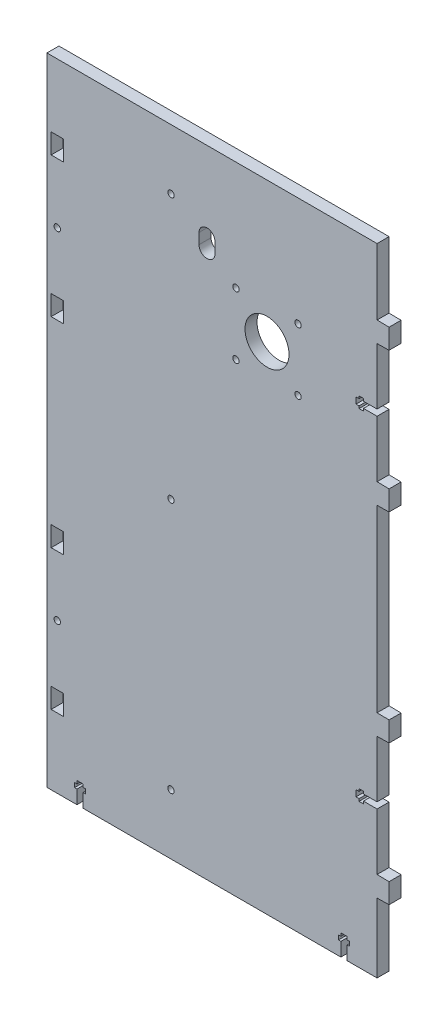
SolidWorks part; units mm, degrees
material "Клен"
ref_plane "Front" through (0, 0, 0) normal (0, 0, 1) x (1, 0, 0)
ref_plane "Top" through (0, 0, 0) normal (0, 1, 0) x (1, 0, 0)
ref_plane "Right" through (0, 0, 0) normal (1, 0, 0) x (0, 0, -1)
sketch "Эскиз1" plane through (0, 0, 0) normal (0, 0, 1) x (1, 0, 0)
  line L1 (976.111, 850.9685) -> (976.111, 499.7864) construction
  line L3 (994.111, 828.857) -> (994.111, 777.5026) construction
  line L4 (1057.0026, 791.3385) -> (985.8343, 791.3385) construction
  line L5 (998.111, 791.3385) -> (998.111, 796.6215)
  line L6 (990.111, 796.6215) -> (990.111, 791.3385)
  line L16 (922.3199, 553.2385) -> (922.3199, 563.2385)
  line L17 (916.2199, 553.2385) -> (922.3199, 553.2385)
  line L18 (916.2199, 563.2385) -> (916.2199, 553.2385)
  line L19 (922.3199, 563.2385) -> (916.2199, 563.2385)
  line L20 (916.2199, 623.2385) -> (922.3199, 623.2385)
  line L21 (922.3199, 623.2385) -> (922.3199, 633.2385)
  line L22 (922.3199, 633.2385) -> (916.2199, 633.2385)
  line L23 (916.2199, 633.2385) -> (916.2199, 623.2385)
  line L24 (916.2199, 723.2385) -> (922.3199, 723.2385)
  line L25 (922.3199, 723.2385) -> (922.3199, 733.2385)
  line L26 (916.2199, 733.2385) -> (916.2199, 723.2385)
  line L27 (922.3199, 733.2385) -> (916.2199, 733.2385)
  line L28 (922.3199, 793.2385) -> (922.3199, 803.2385)
  line L29 (922.3199, 803.2385) -> (916.2199, 803.2385)
  line L30 (916.2199, 803.2385) -> (916.2199, 793.2385)
  line L31 (916.2199, 793.2385) -> (922.3199, 793.2385)
  line L32 (979.111, 858.5777) -> (979.111, 499.7864) construction
  line L33 (1079.111, 858.5777) -> (1079.111, 499.7864) construction
  line L34 (1079.111, 623.0385) -> (1085.111, 623.1385)
  line L35 (1068.611, 764.6885) -> (1070.111, 764.6885)
  line L36 (1085.111, 553.1385) -> (1085.111, 563.1385)
  line L37 (1072.311, 591.5885) -> (1072.311, 590.3885)
  line L38 (1072.311, 761.5885) -> (1072.311, 760.3885)
  line L39 (1072.311, 765.8885) -> (1072.311, 764.6885)
  line L40 (1085.111, 793.1385) -> (1085.111, 803.1385)
  line L41 (1085.111, 723.1385) -> (1085.111, 733.1385)
  line L42 (1068.611, 761.5885) -> (1068.611, 764.6885)
  line L43 (1070.111, 590.3885) -> (1070.111, 591.5885)
  line L44 (1068.611, 591.5885) -> (1068.611, 594.6885)
  line L45 (1085.111, 733.1385) -> (1079.111, 733.2385)
  line L46 (1085.111, 633.1385) -> (1079.111, 633.2385)
  line L47 (1079.111, 633.2385) -> (1079.111, 723.0385)
  line L48 (1085.111, 803.1385) -> (1079.111, 803.2385)
  line L49 (1072.311, 595.8885) -> (1072.311, 594.6885)
  line L50 (1079.111, 793.0385) -> (1085.111, 793.1385)
  line L51 (1079.111, 733.2385) -> (1079.111, 761.5885)
  line L52 (1068.611, 594.6885) -> (1070.111, 594.6885)
  line L53 (1072.311, 760.3885) -> (1070.111, 760.3885)
  line L54 (1070.111, 761.5885) -> (1068.611, 761.5885)
  line L55 (1070.111, 765.8885) -> (1072.311, 765.8885)
  line L112 (932.211, 525.2362) -> (932.211, 518.4362)
  line L113 (932.211, 518.4362) -> (979.111, 518.4362)
  line L155 (979.111, 836.3385) -> (914.111, 836.3385)
  line L156 (914.111, 836.3385) -> (914.111, 518.4362)
  line L157 (914.111, 518.4362) -> (929.111, 518.4362)
  line L158 (929.111, 518.4362) -> (929.111, 525.2362)
  line L159 (929.111, 525.2362) -> (927.911, 525.2362)
  line L160 (927.911, 525.2362) -> (927.911, 527.4362)
  line L161 (927.911, 527.4362) -> (929.111, 527.4362)
  line L162 (929.111, 527.4362) -> (929.111, 528.9362)
  line L163 (929.111, 528.9362) -> (932.211, 528.9362)
  line L164 (932.211, 528.9362) -> (932.211, 527.4362)
  line L165 (932.211, 527.4362) -> (933.411, 527.4362)
  line L166 (933.411, 527.4362) -> (933.411, 525.2362)
  line L167 (933.411, 525.2362) -> (932.211, 525.2362)
  line L168 (1070.111, 594.6885) -> (1070.111, 595.8885)
  line L169 (1079.111, 594.6885) -> (1079.111, 623.0385)
  line L170 (1072.311, 764.6885) -> (1079.111, 764.6885)
  line L171 (1085.111, 563.1385) -> (1079.111, 563.2385)
  line L172 (1085.111, 623.1385) -> (1085.111, 633.1385)
  line L173 (1070.111, 764.6885) -> (1070.111, 765.8885)
  line L174 (1079.111, 553.0385) -> (1085.111, 553.1385)
  line L175 (1079.111, 563.2385) -> (1079.111, 591.5885)
  line L176 (1079.111, 761.5885) -> (1072.311, 761.5885)
  line L177 (1079.111, 518.4362) -> (1079.111, 553.0385)
  line L178 (1070.111, 591.5885) -> (1068.611, 591.5885)
  line L179 (1070.111, 595.8885) -> (1072.311, 595.8885)
  line L180 (1070.111, 760.3885) -> (1070.111, 761.5885)
  line L181 (1079.111, 591.5885) -> (1072.311, 591.5885)
  line L182 (1072.311, 594.6885) -> (1079.111, 594.6885)
  line L183 (1079.111, 803.2385) -> (1079.111, 836.3385)
  line L184 (1072.311, 590.3885) -> (1070.111, 590.3885)
  line L185 (1079.111, 723.0385) -> (1085.111, 723.1385)
  line L186 (1079.111, 764.6885) -> (1079.111, 793.0385)
  line L187 (979.111, 836.3385) -> (1079.111, 836.3385)
  line L188 (979.111, 518.4362) -> (1061.011, 518.4362)
  line L189 (1059.811, 527.4362) -> (1061.011, 527.4362)
  line L190 (1061.011, 518.4362) -> (1061.011, 525.2362)
  line L191 (1065.311, 525.2362) -> (1064.111, 525.2362)
  line L192 (1061.011, 527.4362) -> (1061.011, 528.9362)
  line L193 (1061.011, 528.9362) -> (1064.111, 528.9362)
  line L194 (1061.011, 525.2362) -> (1059.811, 525.2362)
  line L195 (1064.111, 525.2362) -> (1064.111, 518.4362)
  line L196 (1064.111, 528.9362) -> (1064.111, 527.4362)
  line L197 (1064.111, 527.4362) -> (1065.311, 527.4362)
  line L198 (1059.811, 525.2362) -> (1059.811, 527.4362)
  line L199 (1065.311, 527.4362) -> (1065.311, 525.2362)
  line L200 (1064.111, 518.4362) -> (1079.111, 518.4362)
  circle A2 centre (919.2699, 593.2385) radius 1.6
  circle A3 centre (919.2699, 763.2385) radius 1.6
  circle A5 centre (976.111, 806.3385) radius 1.6
  circle A6 centre (976.111, 674.1385) radius 1.6
  circle A7 centre (976.111, 548.4385) radius 1.6
  circle A8 centre (1008.611, 781.8385) radius 1.6
  circle A9 centre (1008.611, 750.8385) radius 1.6
  circle A10 centre (1024.111, 766.3385) radius 11
  circle A11 centre (1039.611, 750.8385) radius 1.6
  circle A12 centre (1039.611, 781.8385) radius 1.6
  arc A15 (998.111, 796.6215) -> (990.111, 796.6215) centre (994.111, 796.6215) ccw
  arc A16 (990.111, 791.3385) -> (998.111, 791.3385) centre (994.111, 791.3385) ccw
  dimension "D5" = 15.5
  dimension "D6" = 31
  dimension "D7" = 31
  dimension "D8" = 31
  dimension "D9" = 31
  dimension "D10" = 45
  dimension "D13" = 3.2
  dimension "D14" = 3.2
  dimension "D15" = 3.2
  dimension "D11" = 70
  dimension "D16" = 30
  dimension "D17" = 25
  dimension "D2" = 100
  dimension "D3" = 65
  dimension "D4" = 15
  dimension "D12" = 103
extrude "Бобышка-Вытянуть1" add sketch "Эскиз1" along normal blind 6
